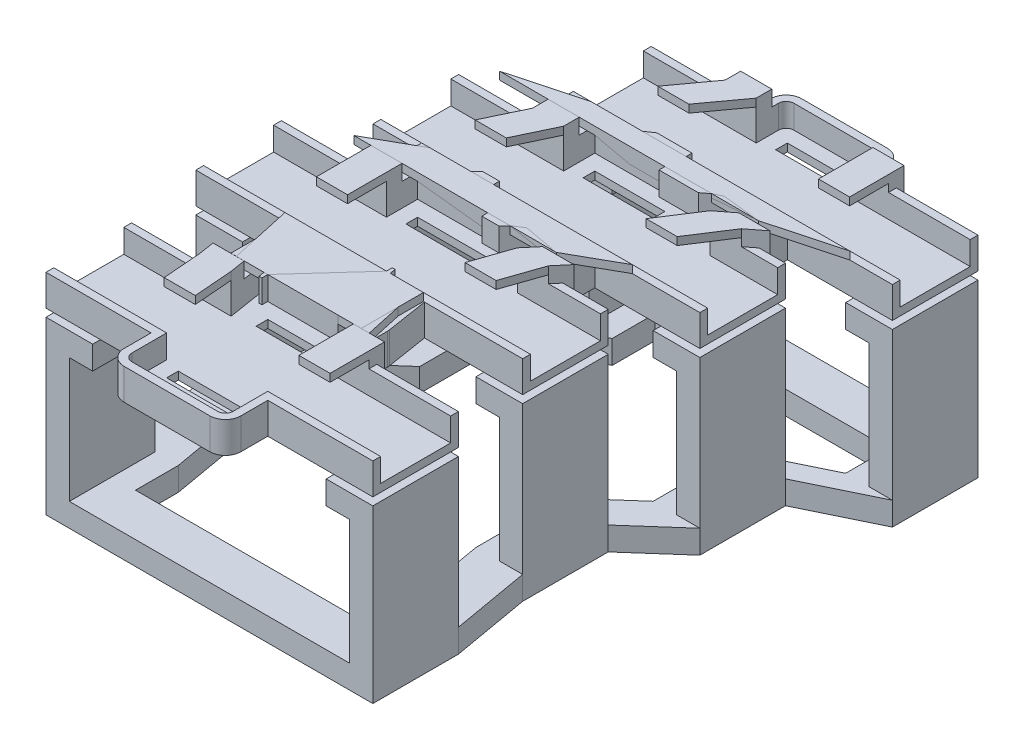
SolidWorks part; units mm, degrees
ref_plane "前视基准面" through (0, 0, 0) normal (0, 0, 1) x (1, 0, 0)
ref_plane "上视基准面" through (0, 0, 0) normal (0, 1, 0) x (1, 0, 0)
ref_plane "右视基准面" through (0, 0, 0) normal (1, 0, 0) x (0, 0, -1)
other "Configuration Table"
sketch "草图4" plane through (0, 0, 0) normal (0, 1, 0) x (1, 0, 0)
  line L0 (0, 0) -> (0, 21)
  line L1 (0, 21) -> (0, 37.5227) construction
  line L2 (0, 37.5227) -> (4, 37.5227) construction
  line L3 (4, 37.5227) -> (0, 21)
  line L4 (0, 37.5227) -> (0, 53.0146) construction
  line L5 (0, 53.0146) -> (8, 53.0146) construction
  line L6 (8, 53.0146) -> (4, 37.5227)
  line L7 (0, 0) -> (-23.5, 0)
  line L8 (0, 21) -> (-25.25, 21)
  line L9 (8, 53.0146) -> (-9.75, 53.0146)
  line L10 (4, 37.5227) -> (-19, 37.5227)
  dimension "D1" = 4
  dimension "D2" = 8
  dimension "D3" = 21
  dimension "D4" = 17
  dimension "D5" = 16
  dimension "D6" = 23.5
  dimension "D7" = 25.25
  dimension "D8" = 23
  dimension "D9" = 17.75
sketch "草图5" plane through (0, 0, 0) normal (0, 1, 0) x (1, 0, 0)
  line L1 (-17, -9.95) -> (-30, -9.95)
  line L2 (-17, -9.95) -> (-17, 9.95)
  line L3 (-17, 9.95) -> (-30, 9.95)
  line L4 (-30, -9.95) -> (-30, 9.95)
  line L5 (-17, -9.95) -> (-30, 9.95) construction
  line L6 (-17, 9.95) -> (-30, -9.95) construction
  line L7 (-18.75, 11.05) -> (-31.75, 11.05)
  line L8 (-18.75, 11.05) -> (-18.75, 30.95)
  line L9 (-18.75, 30.95) -> (-31.75, 30.95)
  line L10 (-31.75, 11.05) -> (-31.75, 30.95)
  line L11 (-18.75, 11.05) -> (-31.75, 30.95) construction
  line L12 (-18.75, 30.95) -> (-31.75, 11.05) construction
  line L13 (-12.5, 28.3727) -> (-25.5, 28.3727)
  line L14 (-12.5, 28.3727) -> (-12.5, 46.6727)
  line L15 (-12.5, 46.6727) -> (-25.5, 46.6727)
  line L16 (-25.5, 28.3727) -> (-25.5, 46.6727)
  line L17 (-12.5, 28.3727) -> (-25.5, 46.6727) construction
  line L18 (-12.5, 46.6727) -> (-25.5, 28.3727) construction
  line L19 (-3.25, 44.6646) -> (-16.25, 44.6646)
  line L20 (-3.25, 44.6646) -> (-3.25, 61.3646)
  line L21 (-3.25, 61.3646) -> (-16.25, 61.3646)
  line L22 (-16.25, 44.6646) -> (-16.25, 61.3646)
  line L23 (-3.25, 44.6646) -> (-16.25, 61.3646) construction
  line L24 (-3.25, 61.3646) -> (-16.25, 44.6646) construction
  line L51 (-12.5, 28.3727) -> (-18.75, 21)
  line L52 (-17, 9.95) -> (-18.75, 21)
  line L53 (-31.75, 11.05) -> (-30, 0)
  line L54 (-31.75, 30.95) -> (-25.5, 37.5227)
  line L55 (-3.25, 44.6646) -> (-12.5, 37.5227)
  line L56 (-25.5, 46.6727) -> (-16.25, 53.0146)
  point P0 (-23.5, 0)
  point P6 (-25.25, 21)
  point P12 (-19, 37.5227)
  point P18 (-9.75, 53.0146)
  dimension "D1" = 13
  dimension "D2" = 13
  dimension "D3" = 13
  dimension "D4" = 13
  dimension "D5" = 19.9
  dimension "D6" = 19.9
  dimension "D7" = 18.3
  dimension "D8" = 16.7
extrude "凸台-拉伸1" add sketch "草图5" along normal blind 1 contours L4 L1 L2 L3 | L13 L16 L9 L10 L7 L8 | L19 L22 L15 L16 L9 L8 L13 L14 | L22 L15 L14 L19 L20 L21 | L7 L53 L4 L3 L52 L8 | L16 L13 L8 L9 | L54 L9 L16 | L51 L13 L8 | L55 L19 L14 | L56 L15 L22 | L22 L19 L14 L15 region at (-23.5, 0, 0) region at (-24.375, 0, -10.5) region at (-25.4753, 0, -20.3756) region at (-16.6667, 0, -25.9151) region at (-22.125, 0, -29.6614) region at (-18.9083, 0, -37.8768) region at (-27.5833, 0, -33.1409) region at (-9.4167, 0, -42.284) region at (-14.375, 0, -45.6687) region at (-9.5838, 0, -53.2786) region at (-19.3333, 0, -48.7867)
ref_plane "基准面1" through (-23.5, 0, 0) normal (1, 0, 0) x (0, 0, -1)
ref_plane "基准面2" through (-25.25, 0, 0) normal (1, 0, 0) x (0, 0, -1)
ref_plane "基准面3" through (-19, 0, 0) normal (1, 0, 0) x (0, 0, -1)
ref_plane "基准面4" through (-9.75, 0, 0) normal (1, 0, 0) x (0, 0, -1)
sketch "草图11" plane through (0, 1, 0) normal (0, 1, 0) x (1, 0, 0)
  line L1 (-28, -6.5) -> (-19, -6.5)
  line L2 (-28, -6.5) -> (-28, 6.5)
  line L3 (-28, 6.5) -> (-19, 6.5)
  line L4 (-19, -6.5) -> (-19, 6.5)
  line L5 (-28, -6.5) -> (-19, 6.5) construction
  line L6 (-28, 6.5) -> (-19, -6.5) construction
  line L7 (-29.75, 14.5) -> (-20.75, 14.5)
  line L8 (-29.75, 14.5) -> (-29.75, 27.5)
  line L9 (-29.75, 27.5) -> (-20.75, 27.5)
  line L10 (-20.75, 14.5) -> (-20.75, 27.5)
  line L11 (-29.75, 14.5) -> (-20.75, 27.5) construction
  line L12 (-29.75, 27.5) -> (-20.75, 14.5) construction
  line L13 (-23.5, 31.0227) -> (-14.5, 31.0227)
  line L14 (-23.5, 31.0227) -> (-23.5, 44.0227)
  line L15 (-23.5, 44.0227) -> (-14.5, 44.0227)
  line L16 (-14.5, 31.0227) -> (-14.5, 44.0227)
  line L17 (-23.5, 31.0227) -> (-14.5, 44.0227) construction
  line L18 (-23.5, 44.0227) -> (-14.5, 31.0227) construction
  line L19 (-14.25, 46.5146) -> (-5.25, 46.5146)
  line L20 (-14.25, 46.5146) -> (-14.25, 59.5146)
  line L21 (-14.25, 59.5146) -> (-5.25, 59.5146)
  line L22 (-5.25, 46.5146) -> (-5.25, 59.5146)
  line L23 (-14.25, 46.5146) -> (-5.25, 59.5146) construction
  line L24 (-14.25, 59.5146) -> (-5.25, 46.5146) construction
  line L25 (-28, -5) -> (-19, -5)
  line L26 (-28, -5) -> (-28, 5)
  line L27 (-28, 5) -> (-19, 5)
  line L28 (-19, -5) -> (-19, 5)
  line L29 (-28, -5) -> (-19, 5) construction
  line L30 (-28, 5) -> (-19, -5) construction
  line L31 (-29.75, 16) -> (-20.75, 16)
  line L32 (-29.75, 16) -> (-29.75, 26)
  line L33 (-29.75, 26) -> (-20.75, 26)
  line L34 (-20.75, 16) -> (-20.75, 26)
  line L35 (-29.75, 16) -> (-20.75, 26) construction
  line L36 (-29.75, 26) -> (-20.75, 16) construction
  line L37 (-23.5, 32.5227) -> (-14.5, 32.5227)
  line L38 (-23.5, 32.5227) -> (-23.5, 42.5227)
  line L39 (-23.5, 42.5227) -> (-14.5, 42.5227)
  line L40 (-14.5, 32.5227) -> (-14.5, 42.5227)
  line L41 (-23.5, 32.5227) -> (-14.5, 42.5227) construction
  line L42 (-23.5, 42.5227) -> (-14.5, 32.5227) construction
  line L43 (-14.25, 48.0146) -> (-5.25, 48.0146)
  line L44 (-14.25, 48.0146) -> (-14.25, 58.0146)
  line L45 (-14.25, 58.0146) -> (-5.25, 58.0146)
  line L46 (-5.25, 48.0146) -> (-5.25, 58.0146)
  line L47 (-14.25, 48.0146) -> (-5.25, 58.0146) construction
  line L48 (-14.25, 58.0146) -> (-5.25, 48.0146) construction
  point P0 (-23.5, 0)
  point P6 (-25.25, 21)
  point P12 (-19, 37.5227)
  point P18 (-9.75, 53.0146)
  point P24 (-23.5, 0)
  point P29 (-25.25, 21)
  point P34 (-19, 37.5227)
  point P39 (-9.75, 53.0146)
  dimension "D1" = 9
  dimension "D2" = 9
  dimension "D3" = 13
  dimension "D4" = 13
  dimension "D5" = 13
  dimension "D6" = 9
  dimension "D7" = 9
  dimension "D8" = 13
  dimension "D9" = 10
  dimension "D10" = 10
  dimension "D11" = 10
  dimension "D12" = 10
extrude "切除-拉伸3" cut sketch "草图11" against normal blind 1 contours L2 L27 L4 L3 | L25 L2 L1 L4 | L31 L8 L7 L10 | L8 L33 L10 L9 | L37 L14 L13 L16 | L14 L39 L16 L15 | L43 L20 L19 L22 | L20 L45 L22 L21 region at (-23.5, 1, 5.75) region at (-23.5, 1, -5.75) region at (-25.25, 1, -15.25) region at (-25.25, 1, -26.75) region at (-19, 1, -31.7727) region at (-19, 1, -43.2727) region at (-9.75, 1, -47.2646) region at (-9.75, 1, -58.7646)
fillet "圆角2" radius 1 15 edges at (-31.75, 0.5, -11.05) (-30, 0.5, 0) (-30, 0.5, 9.95) (-17, 0.5, 9.95) (-17, 0.5, -9.95) (-18.75, 0.5, -21) (-12.5, 0.5, -28.3727) (-12.5, 0.5, -37.5227) (-3.25, 0.5, -44.6646) (-3.25, 0.5, -61.3646) (-16.25, 0.5, -61.3646) (-16.25, 0.5, -53.0146) (-25.5, 0.5, -46.6727) (-25.5, 0.5, -37.5227) (-31.75, 0.5, -30.95)
sketch "草图14" plane through (0, 1, 0) normal (0, 1, 0) x (1, 0, 0)
  line L1 (-43.5, -4.5) -> (-3.5, -4.5)
  line L2 (-43.5, -4.5) -> (-43.5, 4.5)
  line L3 (-43.5, 4.5) -> (-3.5, 4.5)
  line L4 (-3.5, -4.5) -> (-3.5, 4.5)
  line L5 (-43.5, -4.5) -> (-3.5, 4.5) construction
  line L6 (-43.5, 4.5) -> (-3.5, -4.5) construction
  line L7 (-45.25, 16.5) -> (-5.25, 16.5)
  line L8 (-45.25, 16.5) -> (-45.25, 25.5)
  line L9 (-45.25, 25.5) -> (-5.25, 25.5)
  line L10 (-5.25, 16.5) -> (-5.25, 25.5)
  line L11 (-45.25, 16.5) -> (-5.25, 25.5) construction
  line L12 (-45.25, 25.5) -> (-5.25, 16.5) construction
  line L13 (-39, 33.0227) -> (1, 33.0227)
  line L14 (-39, 33.0227) -> (-39, 42.0227)
  line L15 (-39, 42.0227) -> (1, 42.0227)
  line L16 (1, 33.0227) -> (1, 42.0227)
  line L17 (-39, 33.0227) -> (1, 42.0227) construction
  line L18 (-39, 42.0227) -> (1, 33.0227) construction
  line L19 (-29.75, 48.5146) -> (10.25, 48.5146)
  line L20 (-29.75, 48.5146) -> (-29.75, 57.5146)
  line L21 (-29.75, 57.5146) -> (10.25, 57.5146)
  line L22 (10.25, 48.5146) -> (10.25, 57.5146)
  line L23 (-29.75, 48.5146) -> (10.25, 57.5146) construction
  line L24 (-29.75, 57.5146) -> (10.25, 48.5146) construction
  point P0 (-23.5, 0)
  point P6 (-25.25, 21)
  point P12 (-19, 37.5227)
  point P18 (-9.75, 53.0146)
  dimension "D1" = 9
  dimension "D2" = 40
  dimension "D3" = 9
  dimension "D4" = 40
  dimension "D5" = 9
  dimension "D6" = 9
  dimension "D7" = 40
  dimension "D8" = 40
extrude "凸台-拉伸5" add sketch "草图14" against normal blind 1
sketch "草图15" plane through (0, 1, 0) normal (0, 1, 0) x (1, 0, 0)
  line L0 (-17.25, 60.3646) -> (-17.25, 58.5146)
  line L1 (-17.25, 58.5146) -> (-30.75, 58.5146)
  line L2 (-30.75, 58.5146) -> (-30.75, 47.5146)
  line L3 (-30.75, 47.5146) -> (-25.9582, 47.5146)
  line L4 (-25.9582, 47.5146) -> (-25.9582, 47.5146)
  line L5 (-26.5, 46.1459) -> (-26.5, 43.0227)
  line L6 (-26.5, 43.0227) -> (-40, 43.0227)
  line L7 (-40, 43.0227) -> (-40, 32.0227)
  line L8 (-40, 32.0227) -> (-32.1099, 32.0227)
  line L9 (-32.1099, 32.0227) -> (-32.1993, 31.9286)
  line L10 (-32.75, 30.5505) -> (-32.75, 26.5)
  line L11 (-32.75, 26.5) -> (-46.25, 26.5)
  line L12 (-46.25, 26.5) -> (-46.25, 15.5)
  line L13 (-46.25, 15.5) -> (-32.75, 15.5)
  line L14 (-32.75, 15.5) -> (-32.75, 11.1287)
  line L15 (-32.7254, 10.8159) -> (-31.8835, 5.5)
  line L16 (-31.8835, 5.5) -> (-44.5, 5.5)
  line L17 (-44.5, 5.5) -> (-44.5, -5.5)
  line L18 (-44.5, -5.5) -> (-31, -5.5)
  line L19 (-31, -5.5) -> (-31, -8.95)
  line L20 (-29, -10.95) -> (-18, -10.95)
  line L21 (-16, -8.95) -> (-16, -5.5)
  line L22 (-16, -5.5) -> (-2.5, -5.5)
  line L23 (-2.5, -5.5) -> (-2.5, 5.5)
  line L24 (-2.5, 5.5) -> (-16, 5.5)
  line L25 (-16, 5.5) -> (-16, 9.8713)
  line L26 (-16.0246, 10.1841) -> (-16.8665, 15.5)
  line L27 (-16.8665, 15.5) -> (-4.25, 15.5)
  line L28 (-4.25, 15.5) -> (-4.25, 26.5)
  line L29 (-4.25, 26.5) -> (-12.7766, 26.5)
  line L30 (-12.7766, 26.5) -> (-11.9744, 27.4463)
  line L31 (-11.5, 28.7395) -> (-11.5, 32.0227)
  line L32 (-11.5, 32.0227) -> (2, 32.0227)
  line L33 (2, 32.0227) -> (2, 43.0227)
  line L34 (2, 43.0227) -> (-3.7403, 43.0227)
  line L35 (-3.7403, 43.0227) -> (-3.0277, 43.5729)
  line L36 (-2.25, 45.1559) -> (-2.25, 47.5146)
  line L37 (-2.25, 47.5146) -> (11.25, 47.5146)
  line L38 (11.25, 47.5146) -> (11.25, 58.5146)
  line L39 (11.25, 58.5146) -> (-2.25, 58.5146)
  line L40 (-2.25, 58.5146) -> (-2.25, 60.3646)
  line L41 (-4.25, 62.3646) -> (-15.25, 62.3646)
  line L42 (-16.25, 60.3646) -> (-16.25, 57.5146)
  line L43 (-16.25, 57.5146) -> (-29.75, 57.5146)
  line L44 (-29.75, 57.5146) -> (-29.75, 48.5146)
  line L45 (-29.75, 48.5146) -> (-22.8135, 48.5146)
  line L46 (-22.8135, 48.5146) -> (-25.0655, 46.9706)
  line L47 (-25.5, 46.1459) -> (-25.5, 42.0227)
  line L48 (-25.5, 42.0227) -> (-39, 42.0227)
  line L49 (-39, 42.0227) -> (-39, 33.0227)
  line L50 (-39, 33.0227) -> (-29.7791, 33.0227)
  line L51 (-29.7791, 33.0227) -> (-31.4747, 31.2395)
  line L52 (-31.75, 30.5505) -> (-31.75, 25.5)
  line L53 (-31.75, 25.5) -> (-45.25, 25.5)
  line L54 (-45.25, 25.5) -> (-45.25, 16.5)
  line L55 (-45.25, 16.5) -> (-31.75, 16.5)
  line L56 (-31.75, 16.5) -> (-31.75, 11.1287)
  line L57 (-31.7377, 10.9723) -> (-30.7127, 4.5)
  line L58 (-30.7127, 4.5) -> (-43.5, 4.5)
  line L59 (-43.5, 4.5) -> (-43.5, -4.5)
  line L60 (-43.5, -4.5) -> (-30, -4.5)
  line L61 (-30, -4.5) -> (-30, -8.95)
  line L62 (-29, -9.95) -> (-18, -9.95)
  line L63 (-17, -8.95) -> (-17, -4.5)
  line L64 (-17, -4.5) -> (-3.5, -4.5)
  line L65 (-3.5, -4.5) -> (-3.5, 4.5)
  line L66 (-3.5, 4.5) -> (-17, 4.5)
  line L67 (-17, 4.5) -> (-17, 9.8713)
  line L68 (-17.0123, 10.0277) -> (-18.0373, 16.5)
  line L69 (-18.0373, 16.5) -> (-5.25, 16.5)
  line L70 (-5.25, 16.5) -> (-5.25, 25.5)
  line L71 (-5.25, 25.5) -> (-14.9353, 25.5)
  line L72 (-14.9353, 25.5) -> (-12.7372, 28.0929)
  line L73 (-12.5, 28.7395) -> (-12.5, 33.0227)
  line L74 (-12.5, 33.0227) -> (1, 33.0227)
  line L75 (1, 33.0227) -> (1, 42.0227)
  line L76 (1, 42.0227) -> (-6.6717, 42.0227)
  line L77 (-6.6717, 42.0227) -> (-3.6389, 44.3644)
  line L78 (-3.25, 45.1559) -> (-3.25, 48.5146)
  line L79 (-3.25, 48.5146) -> (10.25, 48.5146)
  line L80 (10.25, 48.5146) -> (10.25, 57.5146)
  line L81 (10.25, 57.5146) -> (-3.25, 57.5146)
  line L82 (-3.25, 57.5146) -> (-3.25, 60.3646)
  line L83 (-4.25, 61.3646) -> (-15.25, 61.3646)
  line L84 (-16.25, 60.3646) -> (-16.25, 57.5146)
  line L85 (-16.25, 57.5146) -> (-29.75, 57.5146)
  line L86 (-29.75, 57.5146) -> (-29.75, 48.5146)
  line L87 (-29.75, 48.5146) -> (-22.8135, 48.5146)
  line L88 (-22.8135, 48.5146) -> (-25.0655, 46.9706)
  line L89 (-25.5, 46.1459) -> (-25.5, 42.0227)
  line L90 (-25.5, 42.0227) -> (-39, 42.0227)
  line L91 (-39, 42.0227) -> (-39, 33.0227)
  line L92 (-39, 33.0227) -> (-29.7791, 33.0227)
  line L93 (-29.7791, 33.0227) -> (-31.4747, 31.2395)
  line L94 (-31.75, 30.5505) -> (-31.75, 25.5)
  line L95 (-31.75, 25.5) -> (-45.25, 25.5)
  line L96 (-45.25, 25.5) -> (-45.25, 16.5)
  line L97 (-45.25, 16.5) -> (-31.75, 16.5)
  line L98 (-31.75, 16.5) -> (-31.75, 11.1287)
  line L99 (-31.7377, 10.9723) -> (-30.7127, 4.5)
  line L100 (-30.7127, 4.5) -> (-43.5, 4.5)
  line L101 (-43.5, 4.5) -> (-43.5, -4.5)
  line L102 (-43.5, -4.5) -> (-30, -4.5)
  line L103 (-30, -4.5) -> (-30, -8.95)
  line L104 (-29, -9.95) -> (-18, -9.95)
  line L105 (-17, -8.95) -> (-17, -4.5)
  line L106 (-17, -4.5) -> (-3.5, -4.5)
  line L107 (-3.5, -4.5) -> (-3.5, 4.5)
  line L108 (-3.5, 4.5) -> (-17, 4.5)
  line L109 (-17, 4.5) -> (-17, 9.8713)
  line L110 (-17.0123, 10.0277) -> (-18.0373, 16.5)
  line L111 (-18.0373, 16.5) -> (-5.25, 16.5)
  line L112 (-5.25, 16.5) -> (-5.25, 25.5)
  line L113 (-5.25, 25.5) -> (-14.9353, 25.5)
  line L114 (-14.9353, 25.5) -> (-12.7372, 28.0929)
  line L115 (-12.5, 28.7395) -> (-12.5, 33.0227)
  line L116 (-12.5, 33.0227) -> (1, 33.0227)
  line L117 (1, 33.0227) -> (1, 42.0227)
  line L118 (1, 42.0227) -> (-6.6717, 42.0227)
  line L119 (-6.6717, 42.0227) -> (-3.6389, 44.3644)
  line L120 (-3.25, 45.1559) -> (-3.25, 48.5146)
  line L121 (-3.25, 48.5146) -> (10.25, 48.5146)
  line L122 (10.25, 48.5146) -> (10.25, 57.5146)
  line L123 (10.25, 57.5146) -> (-3.25, 57.5146)
  line L124 (-3.25, 57.5146) -> (-3.25, 60.3646)
  line L125 (-4.25, 61.3646) -> (-15.25, 61.3646)
  arc A0 (-25.9582, 47.5146) -> (-26.5, 46.1459) centre (-24.5, 46.1459) ccw
  arc A1 (-32.1993, 31.9286) -> (-32.75, 30.5505) centre (-30.75, 30.5505) ccw
  arc A2 (-32.75, 11.1287) -> (-32.7254, 10.8159) centre (-30.75, 11.1287) ccw
  arc A3 (-31, -8.95) -> (-29, -10.95) centre (-29, -8.95) ccw
  arc A4 (-18, -10.95) -> (-16, -8.95) centre (-18, -8.95) ccw
  arc A5 (-16, 9.8713) -> (-16.0246, 10.1841) centre (-18, 9.8713) ccw
  arc A6 (-11.9744, 27.4463) -> (-11.5, 28.7395) centre (-13.5, 28.7395) ccw
  arc A7 (-3.0277, 43.5729) -> (-2.25, 45.1559) centre (-4.25, 45.1559) ccw
  arc A8 (-2.25, 60.3646) -> (-4.25, 62.3646) centre (-4.25, 60.3646) ccw
  arc A9 (-15.25, 62.3646) -> (-17.25, 60.3646) centre (-15.25, 60.3646) ccw
  arc A10 (-25.0655, 46.9706) -> (-25.5, 46.1459) centre (-24.5, 46.1459) ccw
  arc A11 (-31.4747, 31.2395) -> (-31.75, 30.5505) centre (-30.75, 30.5505) ccw
  arc A12 (-31.75, 11.1287) -> (-31.7377, 10.9723) centre (-30.75, 11.1287) ccw
  arc A13 (-30, -8.95) -> (-29, -9.95) centre (-29, -8.95) ccw
  arc A14 (-18, -9.95) -> (-17, -8.95) centre (-18, -8.95) ccw
  arc A15 (-17, 9.8713) -> (-17.0123, 10.0277) centre (-18, 9.8713) ccw
  arc A16 (-12.7372, 28.0929) -> (-12.5, 28.7395) centre (-13.5, 28.7395) ccw
  arc A17 (-3.6389, 44.3644) -> (-3.25, 45.1559) centre (-4.25, 45.1559) ccw
  arc A18 (-3.25, 60.3646) -> (-4.25, 61.3646) centre (-4.25, 60.3646) ccw
  arc A19 (-15.25, 61.3646) -> (-16.25, 60.3646) centre (-15.25, 60.3646) ccw
  arc A20 (-25.0655, 46.9706) -> (-25.5, 46.1459) centre (-24.5, 46.1459) ccw
  arc A21 (-31.4747, 31.2395) -> (-31.75, 30.5505) centre (-30.75, 30.5505) ccw
  arc A22 (-31.75, 11.1287) -> (-31.7377, 10.9723) centre (-30.75, 11.1287) ccw
  arc A23 (-30, -8.95) -> (-29, -9.95) centre (-29, -8.95) ccw
  arc A24 (-18, -9.95) -> (-17, -8.95) centre (-18, -8.95) ccw
  arc A25 (-17, 9.8713) -> (-17.0123, 10.0277) centre (-18, 9.8713) ccw
  arc A26 (-12.7372, 28.0929) -> (-12.5, 28.7395) centre (-13.5, 28.7395) ccw
  arc A27 (-3.6389, 44.3644) -> (-3.25, 45.1559) centre (-4.25, 45.1559) ccw
  arc A28 (-3.25, 60.3646) -> (-4.25, 61.3646) centre (-4.25, 60.3646) ccw
  arc A29 (-15.25, 61.3646) -> (-16.25, 60.3646) centre (-15.25, 60.3646) ccw
  dimension "D1" = 0
  dimension "D2" = 1
extrude "凸台-拉伸6" add sketch "草图15" along normal blind 3 and the other way blind 1
sketch "草图16" plane through (0, 4, 0) normal (0, 1, 0) x (1, 0, 0)
  line L0 (-44.5, 5.5) -> (-44.5, -5.5) construction
  line L1 (-44.5, 4.5) -> (-43.5, 4.5)
  line L2 (-44.5, 4.5) -> (-44.5, -4.5)
  line L3 (-44.5, -4.5) -> (-43.5, -4.5)
  line L4 (-43.5, 4.5) -> (-43.5, -4.5)
  line L5 (-30.7127, 4.5) -> (-43.5, 4.5) construction
  line L6 (-2.5, -5.5) -> (-2.5, 5.5) construction
  line L7 (-3.5, -4.5) -> (-2.5, -4.5)
  line L8 (-3.5, -4.5) -> (-3.5, 4.5)
  line L9 (-3.5, 4.5) -> (-2.5, 4.5)
  line L10 (-2.5, -4.5) -> (-2.5, 4.5)
  line L11 (-46.25, 26.5) -> (-46.25, 15.5) construction
  line L12 (-45.25, 25.5) -> (-46.25, 25.5)
  line L13 (-45.25, 25.5) -> (-45.25, 16.5)
  line L14 (-45.25, 16.5) -> (-46.25, 16.5)
  line L15 (-46.25, 25.5) -> (-46.25, 16.5)
  line L16 (-4.25, 15.5) -> (-4.25, 26.5) construction
  line L17 (-5.25, 25.5) -> (-4.25, 25.5)
  line L18 (-5.25, 25.5) -> (-5.25, 16.5)
  line L19 (-5.25, 16.5) -> (-4.25, 16.5)
  line L20 (-4.25, 25.5) -> (-4.25, 16.5)
  line L21 (-40, 43.0227) -> (-40, 32.0227) construction
  line L22 (-39, 42.0227) -> (-40, 42.0227)
  line L23 (-39, 42.0227) -> (-39, 33.0227)
  line L24 (-39, 33.0227) -> (-40, 33.0227)
  line L25 (-40, 42.0227) -> (-40, 33.0227)
  line L26 (2, 32.0227) -> (2, 43.0227) construction
  line L27 (1, 42.0227) -> (2, 42.0227)
  line L28 (1, 42.0227) -> (1, 33.0227)
  line L29 (1, 33.0227) -> (2, 33.0227)
  line L30 (2, 42.0227) -> (2, 33.0227)
  line L31 (11.25, 47.5146) -> (11.25, 58.5146) construction
  line L32 (10.25, 57.5146) -> (11.25, 57.5146)
  line L33 (10.25, 57.5146) -> (10.25, 48.5146)
  line L34 (10.25, 48.5146) -> (11.25, 48.5146)
  line L35 (11.25, 57.5146) -> (11.25, 48.5146)
  line L36 (-30.75, 58.5146) -> (-30.75, 47.5146) construction
  line L37 (-29.75, 57.5146) -> (-30.75, 57.5146)
  line L38 (-29.75, 57.5146) -> (-29.75, 48.5146)
  line L39 (-29.75, 48.5146) -> (-30.75, 48.5146)
  line L40 (-30.75, 57.5146) -> (-30.75, 48.5146)
  line L41 (-29.75, 48.5146) -> (-22.8135, 48.5146) construction
  line L42 (-39, 33.0227) -> (-29.7791, 33.0227) construction
  line L44 (-45.25, 16.5) -> (-31.75, 16.5) construction
  line L45 (-3.5, 4.5) -> (-17, 4.5) construction
extrude "切除-拉伸4" cut sketch "草图16" against normal blind 3
sketch "草图18" plane through (0, 4, 0) normal (0, 1, 0) x (1, 0, 0)
  line L0 (-30, -4.5) -> (-30.7127, 4.5)
  line L1 (-30, -4.5) -> (-34, -4.5)
  line L2 (-30.7127, 4.5) -> (-34.7127, 4.5)
  line L3 (-34, -4.5) -> (-34.7127, 4.5)
  line L4 (-30.7127, 4.5) -> (-44.5, 4.5) construction
  line L5 (-17, -4.5) -> (-17, 4.5)
  line L6 (-17, -4.5) -> (-13, -4.5)
  line L7 (-17, 4.5) -> (-13, 4.5)
  line L8 (-13, -4.5) -> (-13, 4.5)
  line L9 (-2.5, 4.5) -> (-17, 4.5) construction
  line L10 (-31.75, 16.5) -> (-31.75, 25.5)
  line L11 (-31.75, 16.5) -> (-35.75, 16.5)
  line L12 (-31.75, 25.5) -> (-35.75, 25.5)
  line L13 (-35.75, 16.5) -> (-35.75, 25.5)
  line L14 (-31.75, 25.5) -> (-46.25, 25.5) construction
  line L15 (-18.0373, 16.5) -> (-14.9353, 25.5)
  line L16 (-18.0373, 16.5) -> (-14.0373, 16.5)
  line L17 (-14.9353, 25.5) -> (-10.9353, 25.5)
  line L18 (-14.0373, 16.5) -> (-10.9353, 25.5)
  line L19 (-4.25, 25.5) -> (-14.9353, 25.5) construction
  line L20 (-29.7791, 33.0227) -> (-25.5, 42.0227)
  line L21 (-29.7791, 33.0227) -> (-33.7791, 33.0227)
  line L22 (-25.5, 42.0227) -> (-29.5, 42.0227)
  line L23 (-33.7791, 33.0227) -> (-29.5, 42.0227)
  line L24 (-25.5, 42.0227) -> (-40, 42.0227) construction
  line L25 (-12.5, 33.0227) -> (-6.6717, 42.0227)
  line L26 (-12.5, 33.0227) -> (-8.5, 33.0227)
  line L27 (-6.6717, 42.0227) -> (-2.6717, 42.0227)
  line L28 (-8.5, 33.0227) -> (-2.6717, 42.0227)
  line L29 (2, 42.0227) -> (-6.6717, 42.0227) construction
  line L30 (-22.8135, 48.5146) -> (-16.25, 57.5146)
  line L31 (-22.8135, 48.5146) -> (-26.8135, 48.5146)
  line L32 (-16.25, 57.5146) -> (-20.25, 57.5146)
  line L33 (-26.8135, 48.5146) -> (-20.25, 57.5146)
  line L34 (-16.25, 57.5146) -> (-30.75, 57.5146) construction
  line L35 (-3.25, 57.5146) -> (-3.25, 48.5146)
  line L36 (-3.25, 57.5146) -> (0.75, 57.5146)
  line L37 (-3.25, 48.5146) -> (0.75, 48.5146)
  line L38 (0.75, 57.5146) -> (0.75, 48.5146)
  line L39 (-3.25, 48.5146) -> (11.25, 48.5146) construction
  line L40 (-34.3167, -0.5) -> (-30.3167, -0.5)
  line L41 (-17, -0.5) -> (-13, -0.5)
  line L42 (-35.75, 20.5) -> (-31.75, 20.5)
  line L43 (-16.6586, 20.5) -> (-12.6586, 20.5)
  line L44 (-18.0373, 16.5) -> (-4.25, 16.5) construction
  line L45 (-31.8773, 37.0227) -> (-27.8773, 37.0227)
  line L46 (-9.9097, 37.0227) -> (-5.9097, 37.0227)
  line L47 (-12.5, 33.0227) -> (2, 33.0227) construction
  line L48 (-23.8964, 52.5146) -> (-19.8964, 52.5146)
  line L49 (-3.25, 52.5146) -> (0.75, 52.5146)
  point P68 (-32, -4.5)
  line M23 (-46.25, 25.5) -> (-31.75, 25.5)
  dimension "D1" = 4
  dimension "D2" = 4
  dimension "D3" = 4
  dimension "D4" = 4
  dimension "D5" = 4
  dimension "D6" = 4
  dimension "D7" = 4
  dimension "D8" = 4
  dimension "D9" = 4
  dimension "D10" = 4
  dimension "D11" = 4
  dimension "D12" = 4
  dimension "D13" = 4
extrude "凸台-拉伸8" add sketch "草图18" along normal blind 1 from offset 1 separate body contours L33 L48 L30 L32 | L35 L49 L38 L36 | L23 L45 L20 L22 | L25 L46 L28 L27 | L13 L42 L10 M23 | L15 L43 L18 L17 | L3 L40 L0 L2 | L5 L41 L8 L7 region at (-32.5147, 4, -2) region at (-15, 4, -2) region at (-33.75, 4, -23) region at (-13.7969, 4, -23) region at (-28.6886, 4, -39.5227) region at (-6.2907, 4, -39.5227) region at (-20.0732, 4, -55.0146) region at (-1.25, 4, -55.0146)
sketch "草图19" plane through (0, 4, 0) normal (0, 1, 0) x (1, 0, 0)
  line L0 (-34.7127, 4.5) -> (-30.7127, 4.5)
  line L1 (-34.7127, 4.5) -> (-34.871, 5.5)
  line L2 (-30.7127, 4.5) -> (-30.871, 5.5)
  line L3 (-34.871, 5.5) -> (-30.871, 5.5)
  line L4 (-31.8835, 5.5) -> (-44.5, 5.5) construction
  line L7 (-31.7377, 10.9723) -> (-30.7127, 4.5) construction
  line L8 (-13, 4.5) -> (-17, 4.5)
  line L9 (-13, 4.5) -> (-13, 5.5)
  line L10 (-17, 4.5) -> (-17, 5.5)
  line L11 (-13, 5.5) -> (-17, 5.5)
  line L20 (-17, 4.5) -> (-17, 9.8713) construction
  line L21 (-2.5, 5.5) -> (-16, 5.5) construction
  line L22 (-10.9353, 25.5) -> (-14.9353, 25.5)
  line L23 (-10.9353, 25.5) -> (-10.0875, 26.5)
  line L24 (-14.9353, 25.5) -> (-14.0875, 26.5)
  line L25 (-10.0875, 26.5) -> (-14.0875, 26.5)
  line L26 (-12.7372, 28.0929) -> (-14.9353, 25.5) construction
  line L27 (-31.75, 25.5) -> (-35.75, 25.5)
  line L28 (-31.75, 25.5) -> (-31.75, 26.5)
  line L29 (-35.75, 25.5) -> (-35.75, 26.5)
  line L30 (-31.75, 26.5) -> (-35.75, 26.5)
  line L31 (-31.75, 25.5) -> (-46.25, 25.5) construction
  line L32 (-35.75, 25.5) -> (-31.75, 25.5) construction
  line L33 (-32.75, 26.5) -> (-46.25, 26.5) construction
  line L34 (-35.75, 20.5) -> (-35.75, 25.5) construction
  line L35 (-31.75, 30.5505) -> (-31.75, 25.5) construction
  line L36 (-4.25, 26.5) -> (-12.7766, 26.5) construction
  line L37 (-2.6717, 42.0227) -> (-6.6717, 42.0227)
  line L38 (-2.6717, 42.0227) -> (-1.3766, 43.0227)
  line L39 (-6.6717, 42.0227) -> (-5.3766, 43.0227)
  line L40 (-1.3766, 43.0227) -> (-5.3766, 43.0227)
  line L41 (-3.6389, 44.3644) -> (-6.6717, 42.0227) construction
  line L42 (-29.5, 42.0227) -> (-25.5, 42.0227)
  line L43 (-29.5, 42.0227) -> (-29.5, 43.0227)
  line L44 (-25.5, 42.0227) -> (-25.5, 43.0227)
  line L45 (-29.5, 43.0227) -> (-25.5, 43.0227)
  line L46 (-25.5, 42.0227) -> (-25.5, 46.1459) construction
  line L47 (-26.5, 43.0227) -> (-40, 43.0227) construction
  line L48 (2, 43.0227) -> (-3.7403, 43.0227) construction
  line L49 (-20.25, 57.5146) -> (-16.25, 57.5146)
  line L50 (-20.25, 57.5146) -> (-20.25, 58.5146)
  line L51 (-16.25, 57.5146) -> (-16.25, 58.5146)
  line L52 (-20.25, 58.5146) -> (-16.25, 58.5146)
  line L53 (-16.25, 57.5146) -> (-16.25, 60.3646) construction
  line L54 (0.75, 57.5146) -> (-3.25, 57.5146)
  line L55 (0.75, 57.5146) -> (0.75, 58.5146)
  line L56 (-3.25, 57.5146) -> (-3.25, 58.5146)
  line L57 (0.75, 58.5146) -> (-3.25, 58.5146)
  line L60 (11.25, 58.5146) -> (-2.25, 58.5146) construction
  line L61 (-17.25, 58.5146) -> (-30.75, 58.5146) construction
extrude "凸台-拉伸9" add sketch "草图19" along normal blind 2
sketch "草图21" plane through (0, 1, 0) normal (0, 1, 0) x (1, 0, 0)
  line L0 (-29.75, 14.5) -> (-20.75, 14.5)
  line L1 (-29.75, 14.5) -> (-28, 6.5)
  line L2 (-20.75, 14.5) -> (-19, 6.5)
  line L3 (-28, 6.5) -> (-19, 6.5)
  line L4 (-23.5, 31.0227) -> (-14.5, 31.0227)
  line L5 (-23.5, 31.0227) -> (-29.75, 27.5)
  line L6 (-14.5, 31.0227) -> (-20.75, 27.5)
  line L7 (-29.75, 27.5) -> (-20.75, 27.5)
  line L8 (-14.25, 46.5146) -> (-5.25, 46.5146)
  line L9 (-14.25, 46.5146) -> (-23.5, 44.0227)
  line L10 (-5.25, 46.5146) -> (-14.5, 44.0227)
  line L11 (-23.5, 44.0227) -> (-14.5, 44.0227)
extrude "凸台-拉伸11" add sketch "草图21" along normal blind 2 from offset 3 separate body
sketch "草图22" plane through (0, 6, 0) normal (0, 1, 0) x (1, 0, 0)
  line L0 (-19, 6.5) -> (-20.75, 14.5)
  line L1 (-19, 6.5) -> (-14.9581, 6.5)
  line L2 (-20.75, 14.5) -> (-16.7081, 14.5)
  line L3 (-14.9581, 6.5) -> (-16.7081, 14.5)
  line L4 (-16.0246, 10.1841) -> (-16.8665, 15.5) construction
  line L5 (-29.75, 14.5) -> (-28, 6.5)
  line L6 (-29.75, 14.5) -> (-33.7919, 14.5)
  line L7 (-28, 6.5) -> (-32.0419, 6.5)
  line L8 (-33.7919, 14.5) -> (-32.0419, 6.5)
  line L9 (-32.7254, 10.8159) -> (-31.8835, 5.5) construction
  line L10 (-20.75, 14.5) -> (-29.75, 14.5) construction
  line L11 (-14.5, 31.0227) -> (-20.75, 27.5)
  line L12 (-14.5, 31.0227) -> (-5.6789, 31.0227)
  line L13 (-20.75, 27.5) -> (-11.9289, 27.5)
  line L14 (-5.6789, 31.0227) -> (-11.9289, 27.5)
  line L15 (-12.7766, 26.5) -> (-11.9744, 27.4463) construction
  line L16 (-29.75, 27.5) -> (-23.5, 31.0227)
  line L17 (-29.75, 27.5) -> (-37.9309, 27.5)
  line L18 (-23.5, 31.0227) -> (-31.6809, 31.0227)
  line L19 (-37.9309, 27.5) -> (-31.6809, 31.0227)
  line L20 (-29.7791, 33.0227) -> (-31.4747, 31.2395) construction
  line L21 (-14.5, 31.0227) -> (-23.5, 31.0227) construction
  line L22 (-5.25, 46.5146) -> (-14.5, 44.0227)
  line L23 (-5.25, 46.5146) -> (6.8049, 46.5146)
  line L24 (-14.5, 44.0227) -> (-2.4451, 44.0227)
  line L25 (6.8049, 46.5146) -> (-2.4451, 44.0227)
  line L26 (-3.7403, 43.0227) -> (-3.0277, 43.5729) construction
  line L27 (-23.5, 44.0227) -> (-14.25, 46.5146)
  line L28 (-23.5, 44.0227) -> (-35.7157, 44.0227)
  line L29 (-14.25, 46.5146) -> (-26.4657, 46.5146)
  line L30 (-35.7157, 44.0227) -> (-26.4657, 46.5146)
  line L31 (-5.25, 46.5146) -> (-14.25, 46.5146) construction
  arc A0 (-25.9582, 47.5146) -> (-26.5, 46.1459) centre (-24.5, 46.1459) ccw construction
extrude "凸台-拉伸12" add sketch "草图22" against normal blind 1
sketch "草图23" plane through (0, 6, 0) normal (0, 1, 0) x (1, 0, 0)
  line L0 (-17, 5.5) -> (-13, 5.5)
  line L1 (-17, 5.5) -> (-17, 6.5)
  line L2 (-13, 5.5) -> (-13, 6.5)
  line L3 (-17, 6.5) -> (-13, 6.5)
  line L4 (-34.871, 5.5) -> (-30.871, 5.5)
  line L5 (-34.871, 5.5) -> (-35.0275, 6.4877)
  line L6 (-30.871, 5.5) -> (-31.0275, 6.4877)
  line L7 (-35.0275, 6.4877) -> (-31.0275, 6.4877)
  line L10 (-35.75, 26.5) -> (-31.75, 26.5)
  line L11 (-35.75, 26.5) -> (-35.75, 27.5)
  line L12 (-31.75, 26.5) -> (-31.75, 27.5)
  line L13 (-35.75, 27.5) -> (-31.75, 27.5)
  line L14 (-31.75, 30.5505) -> (-31.75, 26.5) construction
  line L15 (-10.0875, 26.5) -> (-14.0875, 26.5)
  line L16 (-10.0875, 26.5) -> (-9.4409, 27.2628)
  line L17 (-14.0875, 26.5) -> (-13.4409, 27.2628)
  line L18 (-9.4409, 27.2628) -> (-13.4409, 27.2628)
  line L19 (-12.7372, 28.0929) -> (-14.9353, 25.5) construction
  line L20 (-29.5, 43.0227) -> (-25.5, 43.0227)
  line L21 (-29.5, 43.0227) -> (-29.5, 44.0227)
  line L22 (-25.5, 43.0227) -> (-25.5, 44.0227)
  line L23 (-29.5, 44.0227) -> (-25.5, 44.0227)
  line L24 (-25.5, 42.0227) -> (-25.5, 46.1459) construction
  line L25 (-1.3766, 43.0227) -> (-5.3766, 43.0227)
  line L26 (-1.3766, 43.0227) -> (-0.5851, 43.6338)
  line L27 (-5.3766, 43.0227) -> (-4.5851, 43.6338)
  line L28 (-0.5851, 43.6338) -> (-4.5851, 43.6338)
  line L29 (-3.6389, 44.3644) -> (-6.6717, 42.0227) construction
  line L30 (-20.25, 58.5146) -> (-16.25, 58.5146)
  line L31 (-20.25, 58.5146) -> (-20.25, 59.5146)
  line L32 (-16.25, 58.5146) -> (-16.25, 59.5146)
  line L33 (-20.25, 59.5146) -> (-16.25, 59.5146)
  line L34 (-16.25, 57.5146) -> (-16.25, 60.3646) construction
  line L35 (0.75, 58.5146) -> (-3.25, 58.5146)
  line L36 (0.75, 58.5146) -> (0.75, 59.5146)
  line L37 (-3.25, 58.5146) -> (-3.25, 59.5146)
  line L38 (0.75, 59.5146) -> (-3.25, 59.5146)
  line L39 (-3.25, 57.5146) -> (-3.25, 60.3646) construction
  line L40 (-17, 5.5) -> (-17, 9.8713) construction
  line L41 (-31.7377, 10.9723) -> (-30.871, 5.5) construction
  dimension "D1" = 1
  dimension "D2" = 1
  dimension "D3" = 1
  dimension "D4" = 1
  dimension "D5" = 1
  dimension "D6" = 1
  dimension "D7" = 1
  dimension "D8" = 1
extrude "凸台-拉伸13" add sketch "草图23" against normal blind 6
sketch "草图24" plane through (0, 0, 0) normal (0, -1, 0) x (1, 0, 0)
  line L0 (-34.871, -5.5) -> (-44.5, -5.5) construction
  line L1 (-44.5, 5.5) -> (-41.5, 5.5)
  line L2 (-44.5, 5.5) -> (-44.5, -5.5)
  line L3 (-44.5, -5.5) -> (-41.5, -5.5)
  line L4 (-41.5, 5.5) -> (-41.5, -5.5)
  line L5 (-2.5, -5.5) -> (-13, -5.5) construction
  line L6 (-2.5, 5.5) -> (-5.5, 5.5)
  line L7 (-2.5, 5.5) -> (-2.5, -5.5)
  line L8 (-2.5, -5.5) -> (-5.5, -5.5)
  line L9 (-5.5, 5.5) -> (-5.5, -5.5)
  line L10 (-35.75, -26.5) -> (-46.25, -26.5) construction
  line L11 (-46.25, -15.5) -> (-43.25, -15.5)
  line L12 (-46.25, -15.5) -> (-46.25, -26.5)
  line L13 (-46.25, -26.5) -> (-43.25, -26.5)
  line L14 (-43.25, -15.5) -> (-43.25, -26.5)
  line L15 (-4.25, -26.5) -> (-10.0875, -26.5) construction
  line L16 (-4.25, -15.5) -> (-7.25, -15.5)
  line L17 (-4.25, -15.5) -> (-4.25, -26.5)
  line L18 (-4.25, -26.5) -> (-7.25, -26.5)
  line L19 (-7.25, -15.5) -> (-7.25, -26.5)
  line L20 (-29.5, -43.0227) -> (-40, -43.0227) construction
  line L21 (-40, -32.0227) -> (-37, -32.0227)
  line L22 (-40, -32.0227) -> (-40, -43.0227)
  line L23 (-40, -43.0227) -> (-37, -43.0227)
  line L24 (-37, -32.0227) -> (-37, -43.0227)
  line L25 (-11.5, -32.0227) -> (2, -32.0227) construction
  line L26 (2, -43.0227) -> (-1, -43.0227)
  line L27 (2, -43.0227) -> (2, -32.0227)
  line L28 (2, -32.0227) -> (-1, -32.0227)
  line L29 (-1, -43.0227) -> (-1, -32.0227)
  line L30 (-20.25, -58.5146) -> (-30.75, -58.5146) construction
  line L31 (-30.75, -47.5146) -> (-27.75, -47.5146)
  line L32 (-30.75, -47.5146) -> (-30.75, -58.5146)
  line L33 (-30.75, -58.5146) -> (-27.75, -58.5146)
  line L34 (-27.75, -47.5146) -> (-27.75, -58.5146)
  line L35 (-2.25, -47.5146) -> (11.25, -47.5146) construction
  line L36 (11.25, -58.5146) -> (8.25, -58.5146)
  line L37 (11.25, -58.5146) -> (11.25, -47.5146)
  line L38 (11.25, -47.5146) -> (8.25, -47.5146)
  line L39 (8.25, -58.5146) -> (8.25, -47.5146)
  line L40 (-41.5, -5.5) -> (-43.25, -15.5)
  line L41 (-44.5, -5.5) -> (-46.25, -15.5)
  line L42 (-5.5, -5.5) -> (-7.25, -15.5)
  line L43 (-2.5, -5.5) -> (-4.25, -15.5)
  line L44 (-46.25, -26.5) -> (-40, -32.0227)
  line L45 (-43.25, -26.5) -> (-37, -32.0227)
  line L46 (-7.25, -26.5) -> (-1, -32.0227)
  line L47 (2, -32.0227) -> (-4.25, -26.5)
  line L48 (-37, -43.0227) -> (-27.75, -47.5146)
  line L49 (-40, -43.0227) -> (-30.75, -47.5146)
  line L50 (2, -43.0227) -> (11.25, -47.5146)
  line L51 (-1, -43.0227) -> (8.25, -47.5146)
  dimension "D1" = 3
  dimension "D2" = 3
  dimension "D3" = 3
  dimension "D4" = 3
  dimension "D5" = 3
  dimension "D6" = 3
  dimension "D7" = 3
  dimension "D8" = 3
extrude "凸台-拉伸14" add sketch "草图24" along normal blind 22 from offset 1 separate body contours L6 L9 L8 L7 | L16 L19 L18 L17 | L29 L26 L27 L28 | L39 L36 L37 L38 | L24 L21 L22 L23 | L34 L31 L32 L33 | L14 L11 L12 L13 | L4 L1 L2 L3 region at (-43, 0, 0) region at (-44.75, 0, -21) region at (-38.5, 0, -37.5227) region at (-29.25, 0, -53.0146) region at (-4, 0, 0) region at (-5.75, 0, -21) region at (0.5, 0, -37.5227) region at (9.75, 0, -53.0146)
sketch "草图25" plane through (0, 0, 0) normal (0, -1, 0) x (1, 0, 0)
  line L0 (-34.871, -5.5) -> (-44.5, -5.5) construction
  line L1 (-41.5, 5.5) -> (-38.5, 5.5)
  line L2 (-41.5, 5.5) -> (-41.5, -5.5)
  line L3 (-41.5, -5.5) -> (-38.5, -5.5)
  line L4 (-38.5, 5.5) -> (-38.5, -5.5)
  line L5 (-2.5, -5.5) -> (-13, -5.5) construction
  line L6 (-5.5, 5.5) -> (-8.5, 5.5)
  line L7 (-5.5, 5.5) -> (-5.5, -5.5)
  line L8 (-5.5, -5.5) -> (-8.5, -5.5)
  line L9 (-8.5, 5.5) -> (-8.5, -5.5)
  line L10 (-35.75, -26.5) -> (-46.25, -26.5) construction
  line L11 (-43.25, -15.5) -> (-40.25, -15.5)
  line L12 (-43.25, -15.5) -> (-43.25, -26.5)
  line L13 (-43.25, -26.5) -> (-40.25, -26.5)
  line L14 (-40.25, -15.5) -> (-40.25, -26.5)
  line L15 (-29.5, -43.0227) -> (-40, -43.0227) construction
  line L16 (-7.25, -15.5) -> (-10.25, -15.5)
  line L17 (-7.25, -15.5) -> (-7.25, -26.5)
  line L18 (-7.25, -26.5) -> (-10.25, -26.5)
  line L19 (-10.25, -15.5) -> (-10.25, -26.5)
  line L20 (-37, -32.0227) -> (-34, -32.0227)
  line L21 (-37, -32.0227) -> (-37, -43.0227)
  line L22 (-37, -43.0227) -> (-34, -43.0227)
  line L23 (-34, -32.0227) -> (-34, -43.0227)
  line L24 (-11.5, -32.0227) -> (2, -32.0227) construction
  line L25 (-1, -43.0227) -> (-4, -43.0227)
  line L26 (-1, -43.0227) -> (-1, -32.0227)
  line L27 (-1, -32.0227) -> (-4, -32.0227)
  line L28 (-4, -43.0227) -> (-4, -32.0227)
  line L29 (-20.25, -58.5146) -> (-30.75, -58.5146) construction
  line L30 (-27.75, -47.5146) -> (-24.75, -47.5146)
  line L31 (-27.75, -47.5146) -> (-27.75, -58.5146)
  line L32 (-27.75, -58.5146) -> (-24.75, -58.5146)
  line L33 (-24.75, -47.5146) -> (-24.75, -58.5146)
  line L34 (-2.25, -47.5146) -> (11.25, -47.5146) construction
  line L35 (8.25, -58.5146) -> (5.25, -58.5146)
  line L36 (8.25, -58.5146) -> (8.25, -47.5146)
  line L37 (8.25, -47.5146) -> (5.25, -47.5146)
  line L38 (5.25, -58.5146) -> (5.25, -47.5146)
  dimension "D1" = 3
  dimension "D2" = 3
  dimension "D3" = 3
  dimension "D4" = 3
  dimension "D5" = 3
  dimension "D6" = 3
  dimension "D7" = 3
  dimension "D8" = 3
extrude "凸台-拉伸15" add sketch "草图25" along normal blind 3 from offset 1
sketch "草图26" plane through (0, -23, 0) normal (0, -1, 0) x (1, 0, 0)
  line L0 (-44.5, -5.5) -> (-41.5, -5.5)
  line L1 (-44.5, 5.5) -> (-41.5, 5.5)
  line L2 (-44.5, 5.5) -> (-44.5, -5.5)
  line L3 (-44.5, -5.5) -> (-41.5, -5.5)
  line L4 (-41.5, 5.5) -> (-41.5, -5.5)
  line L5 (-44.5, -5.5) -> (-46.25, -15.5)
  line L6 (-41.5, -5.5) -> (-43.25, -15.5)
  line L7 (-46.25, -15.5) -> (-43.25, -15.5)
  line L8 (-43.25, -26.5) -> (-43.25, -15.5)
  line L9 (-43.25, -15.5) -> (-46.25, -15.5)
  line L10 (-46.25, -15.5) -> (-46.25, -26.5)
  line L11 (-46.25, -26.5) -> (-43.25, -26.5)
  line L12 (-43.25, -26.5) -> (-43.25, -15.5)
  line L13 (-43.25, -15.5) -> (-46.25, -15.5)
  line L14 (-46.25, -15.5) -> (-46.25, -26.5)
  line L15 (-46.25, -26.5) -> (-43.25, -26.5)
  line L16 (-2.5, 5.5) -> (-5.5, 5.5)
  line L17 (-5.5, 5.5) -> (-5.5, -5.5)
  line L18 (-5.5, -5.5) -> (-2.5, -5.5)
  line L19 (-2.5, -5.5) -> (-2.5, 5.5)
  line L20 (-2.5, 5.5) -> (-5.5, 5.5)
  line L21 (-5.5, 5.5) -> (-5.5, -5.5)
  line L22 (-5.5, -5.5) -> (-2.5, -5.5)
  line L23 (-2.5, -5.5) -> (-2.5, 5.5)
  line L24 (-4.25, -15.5) -> (-7.25, -15.5)
  line L25 (-7.25, -15.5) -> (-7.25, -26.5)
  line L26 (-7.25, -26.5) -> (-4.25, -26.5)
  line L27 (-4.25, -26.5) -> (-4.25, -15.5)
  line L28 (-4.25, -15.5) -> (-7.25, -15.5)
  line L29 (-7.25, -15.5) -> (-7.25, -26.5)
  line L30 (-7.25, -26.5) -> (-4.25, -26.5)
  line L31 (-4.25, -26.5) -> (-4.25, -15.5)
  line L32 (-1, -32.0227) -> (-1, -43.0227)
  line L33 (-1, -43.0227) -> (2, -43.0227)
  line L34 (2, -43.0227) -> (2, -32.0227)
  line L35 (2, -32.0227) -> (-1, -32.0227)
  line L36 (-1, -32.0227) -> (-1, -43.0227)
  line L37 (-1, -43.0227) -> (2, -43.0227)
  line L38 (2, -43.0227) -> (2, -32.0227)
  line L39 (2, -32.0227) -> (-1, -32.0227)
  line L40 (-37, -43.0227) -> (-37, -32.0227)
  line L41 (-37, -32.0227) -> (-40, -32.0227)
  line L42 (-40, -32.0227) -> (-40, -43.0227)
  line L43 (-40, -43.0227) -> (-37, -43.0227)
  line L44 (-37, -43.0227) -> (-37, -32.0227)
  line L45 (-37, -32.0227) -> (-40, -32.0227)
  line L46 (-40, -32.0227) -> (-40, -43.0227)
  line L47 (-40, -43.0227) -> (-37, -43.0227)
  line L48 (-27.75, -58.5146) -> (-27.75, -47.5146)
  line L49 (-27.75, -47.5146) -> (-30.75, -47.5146)
  line L50 (-30.75, -47.5146) -> (-30.75, -58.5146)
  line L51 (-30.75, -58.5146) -> (-27.75, -58.5146)
  line L52 (-27.75, -58.5146) -> (-27.75, -47.5146)
  line L53 (-27.75, -47.5146) -> (-30.75, -47.5146)
  line L54 (-30.75, -47.5146) -> (-30.75, -58.5146)
  line L55 (-30.75, -58.5146) -> (-27.75, -58.5146)
  line L56 (8.25, -47.5146) -> (8.25, -58.5146)
  line L57 (8.25, -58.5146) -> (11.25, -58.5146)
  line L58 (11.25, -58.5146) -> (11.25, -47.5146)
  line L59 (11.25, -47.5146) -> (8.25, -47.5146)
  line L60 (8.25, -47.5146) -> (8.25, -58.5146)
  line L61 (8.25, -58.5146) -> (11.25, -58.5146)
  line L62 (11.25, -58.5146) -> (11.25, -47.5146)
  line L63 (11.25, -47.5146) -> (8.25, -47.5146)
  line L64 (-46.25, -26.5) -> (-43.25, -26.5)
  line L65 (-46.25, -26.5) -> (-40, -32.0227)
  line L66 (-43.25, -26.5) -> (-37, -32.0227)
  line L67 (-40, -32.0227) -> (-37, -32.0227)
  line L68 (-37, -43.0227) -> (-40, -43.0227)
  line L69 (-37, -43.0227) -> (-27.75, -47.5146)
  line L70 (-40, -43.0227) -> (-30.75, -47.5146)
  line L71 (-27.75, -47.5146) -> (-30.75, -47.5146)
  line L72 (8.25, -47.5146) -> (11.25, -47.5146)
  line L73 (8.25, -47.5146) -> (-1, -43.0227)
  line L74 (11.25, -47.5146) -> (2, -43.0227)
  line L75 (-1, -43.0227) -> (2, -43.0227)
  line L76 (2, -32.0227) -> (-1, -32.0227)
  line L77 (2, -32.0227) -> (-4.25, -26.5)
  line L78 (-1, -32.0227) -> (-7.25, -26.5)
  line L79 (-4.25, -26.5) -> (-7.25, -26.5)
  line L80 (-4.25, -15.5) -> (-7.25, -15.5)
  line L81 (-4.25, -15.5) -> (-2.5, -5.5)
  line L82 (-7.25, -15.5) -> (-5.5, -5.5)
  line L83 (-2.5, -5.5) -> (-5.5, -5.5)
  line L84 (8.25, -47.5146) -> (5.25, -47.5146)
  line L85 (-41.5, 5.5) -> (-5.5, 5.5)
  line L86 (-41.5, 5.5) -> (-41.5, 0)
  line L87 (-41.5, 0) -> (-5.5, 0)
  line L88 (-5.5, 5.5) -> (-5.5, 0)
  line L89 (-27.75, -58.5146) -> (8.25, -58.5146)
  line L90 (-27.75, -58.5146) -> (-27.75, -53.0146)
  line L91 (-27.75, -53.0146) -> (8.25, -53.0146)
  line L92 (8.25, -58.5146) -> (8.25, -53.0146)
  line L93 (8.25, -47.5146) -> (-1, -43.0227)
  line L94 (5.25, -47.5146) -> (-4, -43.0227)
  line L95 (-1, -43.0227) -> (-4, -43.0227)
  line L96 (8.25, -58.5146) -> (8.25, -47.5146)
  line L97 (8.25, -47.5146) -> (5.25, -47.5146)
  line L98 (5.25, -47.5146) -> (5.25, -58.5146)
  line L99 (5.25, -58.5146) -> (8.25, -58.5146)
  line L100 (8.25, -58.5146) -> (8.25, -47.5146)
  line L101 (8.25, -47.5146) -> (5.25, -47.5146)
  line L102 (5.25, -47.5146) -> (5.25, -58.5146)
  line L103 (5.25, -58.5146) -> (8.25, -58.5146)
  line L104 (-27.75, -47.5146) -> (-27.75, -58.5146)
  line L105 (-27.75, -58.5146) -> (-24.75, -58.5146)
  line L106 (-24.75, -58.5146) -> (-24.75, -47.5146)
  line L107 (-24.75, -47.5146) -> (-27.75, -47.5146)
  line L108 (-27.75, -47.5146) -> (-27.75, -58.5146)
  line L109 (-27.75, -58.5146) -> (-24.75, -58.5146)
  line L110 (-24.75, -58.5146) -> (-24.75, -47.5146)
  line L111 (-24.75, -47.5146) -> (-27.75, -47.5146)
  line L112 (-1, -43.0227) -> (-1, -32.0227)
  line L113 (-1, -32.0227) -> (-4, -32.0227)
  line L114 (-4, -32.0227) -> (-4, -43.0227)
  line L115 (-4, -43.0227) -> (-1, -43.0227)
  line L116 (-1, -43.0227) -> (-1, -32.0227)
  line L117 (-1, -32.0227) -> (-4, -32.0227)
  line L118 (-4, -32.0227) -> (-4, -43.0227)
  line L119 (-4, -43.0227) -> (-1, -43.0227)
  line L120 (-37, -32.0227) -> (-37, -43.0227)
  line L121 (-37, -43.0227) -> (-34, -43.0227)
  line L122 (-34, -43.0227) -> (-34, -32.0227)
  line L123 (-34, -32.0227) -> (-37, -32.0227)
  line L124 (-37, -32.0227) -> (-37, -43.0227)
  line L125 (-37, -43.0227) -> (-34, -43.0227)
  line L126 (-34, -43.0227) -> (-34, -32.0227)
  line L127 (-34, -32.0227) -> (-37, -32.0227)
  line L128 (-43.25, -15.5) -> (-43.25, -26.5)
  line L129 (-43.25, -26.5) -> (-40.25, -26.5)
  line L130 (-40.25, -26.5) -> (-40.25, -15.5)
  line L131 (-40.25, -15.5) -> (-43.25, -15.5)
  line L132 (-43.25, -15.5) -> (-43.25, -26.5)
  line L133 (-43.25, -26.5) -> (-40.25, -26.5)
  line L134 (-40.25, -26.5) -> (-40.25, -15.5)
  line L135 (-40.25, -15.5) -> (-43.25, -15.5)
  line L136 (-7.25, -26.5) -> (-7.25, -15.5)
  line L137 (-7.25, -15.5) -> (-10.25, -15.5)
  line L138 (-10.25, -15.5) -> (-10.25, -26.5)
  line L139 (-10.25, -26.5) -> (-7.25, -26.5)
  line L140 (-7.25, -26.5) -> (-7.25, -15.5)
  line L141 (-7.25, -15.5) -> (-10.25, -15.5)
  line L142 (-10.25, -15.5) -> (-10.25, -26.5)
  line L143 (-10.25, -26.5) -> (-7.25, -26.5)
  line L144 (-5.5, -5.5) -> (-5.5, 5.5)
  line L145 (-5.5, 5.5) -> (-8.5, 5.5)
  line L146 (-8.5, 5.5) -> (-8.5, -5.5)
  line L147 (-8.5, -5.5) -> (-5.5, -5.5)
  line L148 (-5.5, -5.5) -> (-5.5, 5.5)
  line L149 (-5.5, 5.5) -> (-8.5, 5.5)
  line L150 (-8.5, 5.5) -> (-8.5, -5.5)
  line L151 (-8.5, -5.5) -> (-5.5, -5.5)
  line L152 (-41.5, 5.5) -> (-41.5, -5.5)
  line L153 (-41.5, -5.5) -> (-38.5, -5.5)
  line L154 (-38.5, -5.5) -> (-38.5, 5.5)
  line L155 (-38.5, 5.5) -> (-41.5, 5.5)
  line L156 (-41.5, 5.5) -> (-41.5, -5.5)
  line L157 (-41.5, -5.5) -> (-38.5, -5.5)
  line L158 (-38.5, -5.5) -> (-38.5, 5.5)
  line L159 (-38.5, 5.5) -> (-41.5, 5.5)
  line L160 (-4, -32.0227) -> (-1, -32.0227)
  line L161 (-4, -32.0227) -> (-10.25, -26.5)
  line L162 (-1, -32.0227) -> (-7.25, -26.5)
  line L163 (-10.25, -26.5) -> (-7.25, -26.5)
  line L164 (-7.25, -15.5) -> (-10.25, -15.5)
  line L165 (-7.25, -15.5) -> (-5.5, -5.5)
  line L166 (-10.25, -15.5) -> (-8.5, -5.5)
  line L167 (-5.5, -5.5) -> (-8.5, -5.5)
  line L168 (-38.5, -5.5) -> (-41.5, -5.5)
  line L169 (-38.5, -5.5) -> (-40.25, -15.5)
  line L170 (-41.5, -5.5) -> (-43.25, -15.5)
  line L171 (-40.25, -15.5) -> (-43.25, -15.5)
  line L172 (-40.25, -26.5) -> (-43.25, -26.5)
  line L173 (-40.25, -26.5) -> (-34, -32.0227)
  line L174 (-43.25, -26.5) -> (-37, -32.0227)
  line L175 (-34, -32.0227) -> (-37, -32.0227)
  line L176 (-34, -43.0227) -> (-37, -43.0227)
  line L177 (-34, -43.0227) -> (-24.75, -47.5146)
  line L178 (-37, -43.0227) -> (-27.75, -47.5146)
  line L179 (-24.75, -47.5146) -> (-27.75, -47.5146)
  line M33 (-2.5, 5.5) -> (-5.5, 5.5)
  line M34 (-5.5, 5.5) -> (-5.5, -5.5)
  line M35 (-5.5, -5.5) -> (-2.5, -5.5)
  line M36 (-2.5, -5.5) -> (-2.5, 5.5)
  dimension "D1" = 0
  dimension "D2" = 0
  dimension "D3" = 0
  dimension "D4" = 0
  dimension "D5" = 0
  dimension "D6" = 0
  dimension "D7" = 0
  dimension "D8" = 0
  dimension "D9" = 0
  dimension "D10" = 0
  dimension "D11" = 0
  dimension "D12" = 0
  dimension "D13" = 0
  dimension "D14" = 0
  dimension "D15" = 0
extrude "凸台-拉伸16" add sketch "草图26" against normal blind 3 contours L110 L89 L102 L91 | L62 L63 L60 L61 | L89 L110 L91 L52 | L54 L55 L52 L53 | L110 L111 L52 L91 | L117 L118 L95 L36 | L38 L39 L36 L37 | L73 L95 L94 L84 | L63 L74 L37 L73 | L47 L70 L53 L69 | L177 L125 L69 L111 | L46 L47 L44 L45 | L126 L127 L44 L125 | L66 L15 L65 L45 | L173 L133 L66 L127 | L161 L117 L78 L143 | L78 L39 L77 L30 | L30 L31 L28 L29 | L142 L143 L29 L141 | L14 L15 L12 L7 | L134 L135 L12 L133 | L82 L28 L81 M35 | L166 L141 L82 L151 | L21 M36 M33 M34 M35 | L150 L151 L21 L87 | L85 L150 L87 M34 | L158 L87 L150 L85 | L157 L158 L87 L4 | L87 L158 L85 L4 | L4 L1 L2 L0 | L169 L157 L6 L135 | L5 L7 L6 L0 | L102 L103 L100 L101 region at (-43, -23, 0) region at (-43.875, -23, -10.5) region at (-40.875, -23, -10.5) region at (-40, -23, -2.75) region at (-44.75, -23, -21) region at (-40, -23, 2.75) region at (-41.75, -23, -21) region at (-41.625, -23, -29.2614) region at (-23.5, -23, 2.75) region at (-38.625, -23, -29.2614) region at (-38.5, -23, -37.5227) region at (-7, -23, 2.75) region at (-7, -23, -2.75) region at (-35.5, -23, -37.5227) region at (-33.875, -23, -45.2687) region at (-4, -23, 0) region at (-7.875, -23, -10.5) region at (-30.875, -23, -45.2687) region at (-29.25, -23, -53.0146) region at (-4.875, -23, -10.5) region at (-8.75, -23, -21) region at (-26.25, -23, -50.2646) region at (-5.75, -23, -21) region at (-5.625, -23, -29.2614) region at (-26.25, -23, -55.7646) region at (-2.625, -23, -29.2614) region at (-2.5, -23, -37.5227) region at (-9.75, -23, -55.7646) region at (0.5, -23, -37.5227) region at (2.125, -23, -45.2687) region at (5.125, -23, -45.2687) region at (9.75, -23, -53.0146)
sketch "草图27" plane through (0, 1, 0) normal (0, 1, 0) x (1, 0, 0)
  line L0 (-29.75, 14.5) -> (-20.75, 14.5)
  line L1 (-29.75, 14.5) -> (-28, 6.5)
  line L2 (-20.75, 14.5) -> (-19, 6.5)
  line L3 (-28, 6.5) -> (-19, 6.5)
  line L4 (-29.75, 27.5) -> (-23.5, 31.0227)
  line L5 (-29.75, 27.5) -> (-20.75, 27.5)
  line L6 (-23.5, 31.0227) -> (-14.5, 31.0227)
  line L7 (-20.75, 27.5) -> (-14.5, 31.0227)
  line L8 (-23.5, 44.0227) -> (-14.25, 46.5146)
  line L9 (-23.5, 44.0227) -> (-14.5, 44.0227)
  line L10 (-14.25, 46.5146) -> (-5.25, 46.5146)
  line L11 (-14.5, 44.0227) -> (-5.25, 46.5146)
  line L12 (-29.75, 27.5) -> (-26.4002, 31.0227)
  line L13 (-26.4002, 31.0227) -> (-23.5, 31.0227)
  line L14 (-20.75, 27.5) -> (-17.8498, 27.5)
  line L15 (-17.8498, 27.5) -> (-14.5, 31.0227)
  line L17 (-4.5851, 43.6338) -> (-6.6717, 42.0227) construction
  line L20 (-14.25, 46.5146) -> (-19.8654, 46.5146)
  line L21 (-19.8654, 46.5146) -> (-23.5, 44.0227)
  line L22 (-14.5, 44.0227) -> (-8.4775, 44.0227)
  line L23 (-8.4775, 44.0227) -> (-5.25, 46.5146)
  line L26 (-28, 6.5) -> (-28.483, 6.5)
  line L27 (-28.483, 6.5) -> (-29.75, 14.5)
  line L28 (-20.75, 14.5) -> (-20.267, 14.5)
  line L29 (-20.267, 14.5) -> (-19, 6.5)
  line L32 (-14.5, 43.2727) -> (-9.4488, 43.2727)
  line L33 (-14.5, 42.5227) -> (-14.5, 44.0227) construction
  line L34 (-9.4488, 43.2727) -> (-8.4775, 44.0227)
  line L35 (-14.25, 47.2646) -> (-18.7715, 47.2646)
  line L36 (-14.25, 46.5146) -> (-14.25, 48.0146) construction
  line L37 (-18.7715, 47.2646) -> (-19.8654, 46.5146)
  line L38 (-25.0655, 46.9706) -> (-22.8135, 48.5146) construction
  line L39 (-20.75, 26.75) -> (-18.5629, 26.75)
  line L40 (-20.75, 26) -> (-20.75, 27.5) construction
  line L41 (-18.5629, 26.75) -> (-17.8498, 27.5)
  line L42 (-23.5, 31.7727) -> (-25.6871, 31.7727)
  line L43 (-23.5, 31.0227) -> (-23.5, 32.5227) construction
  line L44 (-25.6871, 31.7727) -> (-26.4002, 31.0227)
  line L45 (-31.4747, 31.2395) -> (-29.7791, 33.0227) construction
  line L46 (-28, 5.75) -> (-28.3643, 5.75)
  line L47 (-28, 5) -> (-28, 6.5) construction
  line L48 (-28.3643, 5.75) -> (-28.483, 6.5)
  line L49 (-20.75, 15.25) -> (-20.3857, 15.25)
  line L50 (-20.75, 14.5) -> (-20.75, 16) construction
  line L51 (-20.3857, 15.25) -> (-20.267, 14.5)
  line L52 (-31.7377, 10.9723) -> (-30.7127, 4.5) construction
  line L53 (-14.25, 47.2646) -> (-14.25, 46.5146)
  line L54 (-14.5, 43.2727) -> (-14.5, 44.0227)
  line L55 (-23.5, 31.7727) -> (-23.5, 31.0227)
  line L56 (-20.75, 26.75) -> (-20.75, 27.5)
  line L57 (-20.75, 15.25) -> (-20.75, 14.5)
  line L58 (-28, 6.5) -> (-28, 5.75)
extrude "凸台-拉伸17" add sketch "草图27" along normal blind 2 from offset 2 separate body contours L49 L57 L28 L51 | L29 L28 L2 | L1 L3 L2 L0 | L58 L26 L48 L46 | L27 L26 L1 | L55 L42 L44 L13 | L13 L12 L4 | L5 L7 L6 L4 | L14 L15 L7 | L56 L39 L41 L14 | L54 L32 L34 L22 | L22 L23 L11 | L9 L11 L10 L8 | L20 L21 L8 | L53 L35 L37 L20 region at (-24.375, 1, -10.5) region at (-28.7443, 1, -9.1667) region at (-20.0057, 1, -11.8333) region at (-20.5368, 1, -14.8575) region at (-28.2132, 1, -6.1425) region at (-26.5501, 1, -29.8485) region at (-22.125, 1, -29.2614) region at (-24.7802, 1, -31.3802) region at (-17.6999, 1, -28.6742) region at (-19.4698, 1, -27.1425) region at (-19.2051, 1, -45.684) region at (-14.375, 1, -45.2687) region at (-16.7941, 1, -46.8762) region at (-9.4092, 1, -44.8534) region at (-11.7245, 1, -43.6587)
sketch "草图28" plane through (0, 5, 0) normal (0, 1, 0) x (1, 0, 0)
  line L8 (-20.3857, 15.25) -> (-20.75, 15.25)
  line L9 (-20.75, 15.25) -> (-20.75, 14.5)
  line L10 (-20.75, 14.5) -> (-29.75, 14.5)
  line L11 (-29.75, 14.5) -> (-28.3643, 5.75)
  line L12 (-28.3643, 5.75) -> (-28, 5.75)
  line L13 (-28, 5.75) -> (-28, 6.5)
  line L14 (-28, 6.5) -> (-19, 6.5)
  line L15 (-19, 6.5) -> (-20.3857, 15.25)
  line L16 (-20.3857, 15.25) -> (-20.75, 15.25)
  line L17 (-20.75, 15.25) -> (-20.75, 14.5)
  line L18 (-20.75, 14.5) -> (-29.75, 14.5)
  line L19 (-29.75, 14.5) -> (-28.3643, 5.75)
  line L20 (-28.3643, 5.75) -> (-28, 5.75)
  line L21 (-28, 5.75) -> (-28, 6.5)
  line L22 (-28, 6.5) -> (-19, 6.5)
  line L23 (-19, 6.5) -> (-20.3857, 15.25)
  line L24 (-23.5, 31.0227) -> (-23.5, 31.7727)
  line L25 (-23.5, 31.7727) -> (-25.6871, 31.7727)
  line L26 (-25.6871, 31.7727) -> (-29.75, 27.5)
  line L27 (-29.75, 27.5) -> (-20.75, 27.5)
  line L28 (-20.75, 27.5) -> (-20.75, 26.75)
  line L29 (-20.75, 26.75) -> (-18.5629, 26.75)
  line L30 (-18.5629, 26.75) -> (-14.5, 31.0227)
  line L31 (-14.5, 31.0227) -> (-23.5, 31.0227)
  line L32 (-23.5, 31.0227) -> (-23.5, 31.7727)
  line L33 (-23.5, 31.7727) -> (-25.6871, 31.7727)
  line L34 (-25.6871, 31.7727) -> (-29.75, 27.5)
  line L35 (-29.75, 27.5) -> (-20.75, 27.5)
  line L36 (-20.75, 27.5) -> (-20.75, 26.75)
  line L37 (-20.75, 26.75) -> (-18.5629, 26.75)
  line L38 (-18.5629, 26.75) -> (-14.5, 31.0227)
  line L39 (-14.5, 31.0227) -> (-23.5, 31.0227)
  line L40 (-14.5, 44.0227) -> (-14.5, 43.2727)
  line L41 (-14.5, 43.2727) -> (-9.4488, 43.2727)
  line L42 (-9.4488, 43.2727) -> (-5.25, 46.5146)
  line L43 (-5.25, 46.5146) -> (-14.25, 46.5146)
  line L44 (-14.25, 46.5146) -> (-14.25, 47.2646)
  line L45 (-14.25, 47.2646) -> (-18.7715, 47.2646)
  line L46 (-18.7715, 47.2646) -> (-23.5, 44.0227)
  line L47 (-23.5, 44.0227) -> (-14.5, 44.0227)
  line L48 (-14.5, 44.0227) -> (-14.5, 43.2727)
  line L49 (-14.5, 43.2727) -> (-9.4488, 43.2727)
  line L50 (-9.4488, 43.2727) -> (-5.25, 46.5146)
  line L51 (-5.25, 46.5146) -> (-14.25, 46.5146)
  line L52 (-14.25, 46.5146) -> (-14.25, 47.2646)
  line L53 (-14.25, 47.2646) -> (-18.7715, 47.2646)
  line L54 (-18.7715, 47.2646) -> (-23.5, 44.0227)
  line L55 (-23.5, 44.0227) -> (-14.5, 44.0227)
  line L68 (-26.5, 46.1459) -> (-26.5, 44.0227) construction
  line L69 (-25.5, 44.0227) -> (-29.5, 44.0227) construction
  line L74 (-12.5, 28.7395) -> (-12.5, 33.0227) construction
  line L75 (-20.75, 14.5) -> (-16, 14.5)
  line L76 (-20.75, 14.5) -> (-20.75, 6.51)
  line L77 (-20.75, 6.51) -> (-16, 6.51)
  line L78 (-16, 14.5) -> (-16, 6.51)
  line L79 (-23.5, 31.0227) -> (-32.75, 31.0227)
  line L80 (-23.5, 31.0227) -> (-23.5, 27.51)
  line L81 (-23.5, 27.51) -> (-32.75, 27.51)
  line L82 (-32.75, 31.0227) -> (-32.75, 27.51)
  line L83 (-20.75, 27.5) -> (-12.5, 27.5)
  line L84 (-20.75, 27.5) -> (-20.75, 31.0227)
  line L85 (-20.75, 31.0227) -> (-12.5, 31.0227)
  line L86 (-12.5, 27.5) -> (-12.5, 31.0227)
  line L87 (-3.25, 45.1559) -> (-3.25, 48.5146) construction
  line L88 (-14.25, 46.5146) -> (-26.5, 46.5146)
  line L89 (-14.25, 46.5146) -> (-14.25, 44.0327)
  line L90 (-14.25, 44.0327) -> (-26.5, 44.0327)
  line L91 (-26.5, 46.5146) -> (-26.5, 44.0327)
  line L92 (-14.5, 44.0227) -> (-3.25, 44.0227)
  line L93 (-14.5, 44.0227) -> (-14.5, 46.5146)
  line L94 (-14.5, 46.5146) -> (-3.25, 46.5146)
  line L95 (-3.25, 44.0227) -> (-3.25, 46.5146)
  line L96 (-31.75, 27.5) -> (-32.75, 27.5) construction
  line L97 (-16, 6.5) -> (-17, 6.5) construction
  line L98 (-32.75, 15.5) -> (-32.75, 11.1287) construction
  line L99 (-28, 6.4977) -> (-32.75, 6.4977)
  line L100 (-28, 6.4977) -> (-28, 14.5)
  line L101 (-28, 14.5) -> (-32.75, 14.5)
  line L102 (-32.75, 6.4977) -> (-32.75, 14.5)
  line L103 (-31.0275, 6.4877) -> (-35.0275, 6.4877) construction
  line L104 (-16, 6.5) -> (-16, 9.8713) construction
  line L105 (-32.75, 30.5505) -> (-32.75, 27.5) construction
  line M68 (-20.3857, 15.25) -> (-20.75, 15.25)
  line M69 (-20.75, 15.25) -> (-20.75, 14.5)
  line M70 (-20.75, 14.5) -> (-29.75, 14.5)
  line M71 (-29.75, 14.5) -> (-28.3643, 5.75)
  line M72 (-28.3643, 5.75) -> (-28, 5.75)
  line M73 (-28, 5.75) -> (-28, 6.5)
  line M74 (-28, 6.5) -> (-19, 6.5)
  line M75 (-19, 6.5) -> (-20.3857, 15.25)
  dimension "D4" = 0.01
  dimension "D5" = 0.01
  dimension "D6" = 0.01
  dimension "D7" = 0.01
  dimension "D1" = 0
  dimension "D2" = 0
  dimension "D3" = 0
extrude "凸台-拉伸18" add sketch "草图28" along normal blind 1 contours L88 L52 L53 L54 | L88 L91 L90 L54 | L55 L93 L88 L54 | L92 L90 L48 L49 L50 | L89 L92 L50 L51 | L92 L95 L94 L50 | L93 L90 L89 L88 | L79 L82 L81 L34 | L79 L32 L33 L34 | L80 L79 L34 L35 | L35 L84 L39 L80 | L84 L83 L38 L39 | L83 L86 L85 L38 | L83 L36 L37 L38 | L76 M70 M74 | L100 M71 | L18 M71 | L78 L75 L77 M75 | L75 L76 L22 M75 | L19 M73 M72 | L75 L23 M69 M68 region at (-20.5368, 5, -14.8575) region at (-17.8355, 5, -10.7368) region at (-20.1323, 5, -9.7499) region at (-24.3736, 5, -10.4988) region at (-28.6181, 5, -11.2559) region at (-30.9147, 5, -10.2663) region at (-28.2131, 5, -6.1413) region at (-24.7802, 5, -31.3802) region at (-25.8869, 5, -29.0524) region at (-22.1538, 5, -29.2501) region at (-18.3602, 5, -29.4763) region at (-30.3108, 5, -29.4753) region at (-14.4647, 5, -28.9938) region at (-19.4698, 5, -27.1425) region at (-11.7245, 5, -43.6587) region at (-10.4986, 5, -45.3592) region at (-5.177, 5, -45.0832) region at (-14.375, 5, -45.2737) region at (-18.1638, 5, -45.1693) region at (-23.9745, 5, -45.4289) region at (-16.7941, 5, -46.8762)
